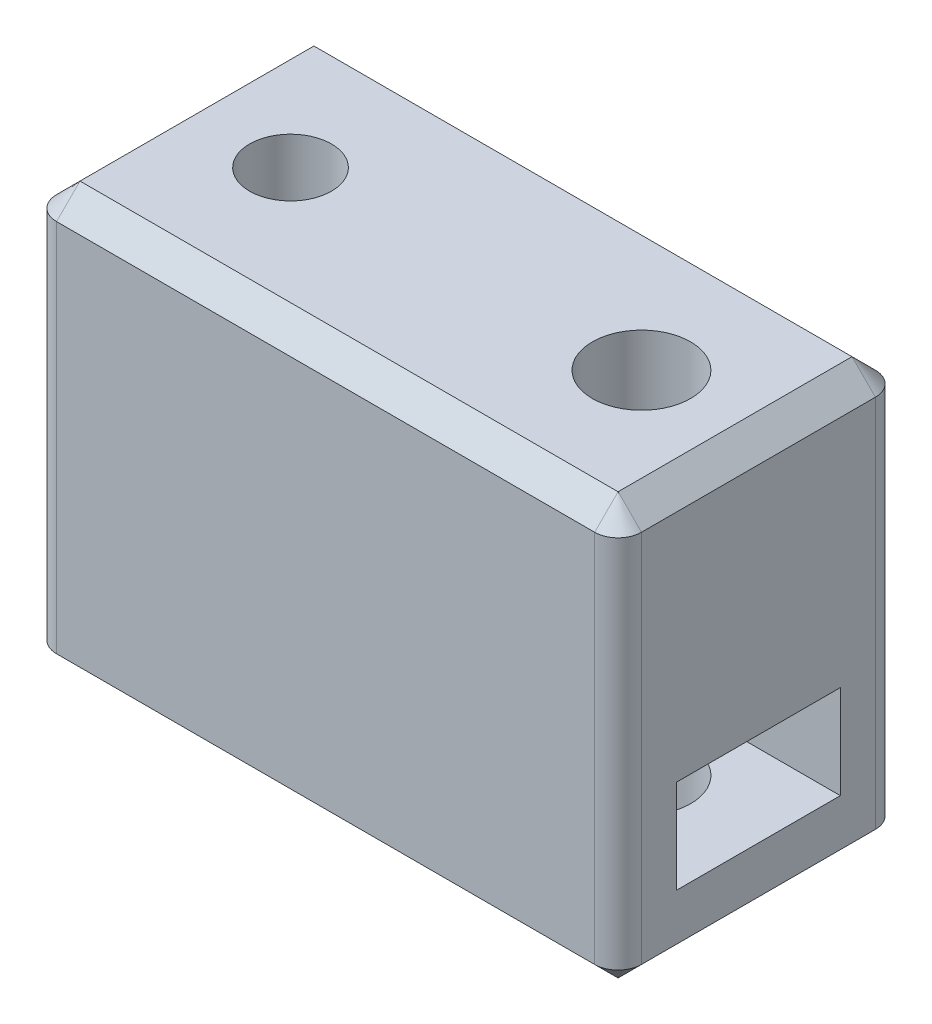
SolidWorks part; units mm, degrees
ref_plane "Front Plane" through (0, 0, 0) normal (0, 0, 1) x (1, 0, 0)
ref_plane "Top Plane" through (0, 0, 0) normal (0, 1, 0) x (1, 0, 0)
ref_plane "Right Plane" through (0, 0, 0) normal (1, 0, 0) x (0, 0, -1)
sketch "Sketch2" plane through (0, 0, 0) normal (0, 1, 0) x (1, 0, 0)
  line L0 (-7.5, 0) -> (7.5, 0) construction
  line L1 (-12.5, 6) -> (12.5, 6)
  line L2 (-12.5, 6) -> (-12.5, -6)
  line L3 (-12.5, -6) -> (12.5, -6)
  line L4 (12.5, 6) -> (12.5, -6)
  line L5 (-12.5, 6) -> (12.5, -6) construction
  line L6 (-12.5, -6) -> (12.5, 6) construction
  circle A0 centre (-7.5, 0) radius 1.75
  circle A1 centre (7.5, 0) radius 2.1
  point P0 (0, 0)
  dimension "D2" = 3.5
  dimension "D3" = 4.2
  dimension "D1" = 12
  dimension "D4" = 5
  dimension "D5" = 15
extrude "Boss-Extrude1" add sketch "Sketch2" along normal blind 18
sketch "Sketch7" plane through (12.5, 0, 0) normal (1, 0, 0) x (0, 0, -1)
  line L0 (0, 0) -> (0, 18) construction
  line L1 (-6, 18) -> (6, 18) construction
  line L2 (-6, 0) -> (6, 0) construction
  line L3 (-3.5, 7) -> (3.5, 7)
  line L4 (-3.5, 7) -> (-3.5, 3)
  line L5 (-3.5, 3) -> (3.5, 3)
  line L6 (3.5, 7) -> (3.5, 3)
  line L7 (-3.5, 7) -> (3.5, 3) construction
  line L8 (-3.5, 3) -> (3.5, 7) construction
  point P5 (0, 5)
  dimension "D1" = 4
  dimension "D2" = 7
  dimension "D3" = 3
extrude "Cut-Extrude3" cut sketch "Sketch7" against normal blind 10
sketch "Sketch9" plane through (-12.5, 0, 0) normal (-1, 0, 0) x (0, 0, 1)
  line L0 (3.5, 3) -> (-3.5, 3) construction
  line L1 (-2.75, 3) -> (2.75, 3)
  line L2 (-2.75, 3) -> (-2.75, 6)
  line L3 (-2.75, 6) -> (2.75, 6)
  line L4 (2.75, 3) -> (2.75, 6)
  line L5 (-2.75, 3) -> (2.75, 6) construction
  line L6 (-2.75, 6) -> (2.75, 3) construction
  line L7 (0, 0) -> (0, 18) construction
  line L8 (-6, 18) -> (6, 18) construction
  point P0 (0, 4.5)
  point P12 (0, 4.5018)
  point P13 (-4.2894, 6)
  point P14 (0, 0)
  dimension "D1" = 3
  dimension "D2" = 5.5
extrude "Cut-Extrude4" cut sketch "Sketch9" against normal blind 8
fillet "Fillet1" radius 1 4 edges at (-12.5, 9, 6) (-12.5, 9, -6) (12.5, 9, -6) (12.5, 9, 6)
chamfer "Chamfer1" distance 1 angle 45 16 edges at (0, 0, -6) (-12.2071, 0, -5.7071) (12.2071, 0, -5.7071) (-12.5, 0, 0) (12.5, 0, 0) (-12.2071, 0, 5.7071) (12.2071, 0, 5.7071) (0, 0, 6) (0, 18, -6) (-12.2071, 18, -5.7071) (12.2071, 18, -5.7071) (-12.5, 18, 0) (12.5, 18, 0) (-12.2071, 18, 5.7071) (12.2071, 18, 5.7071) (0, 18, 6)
